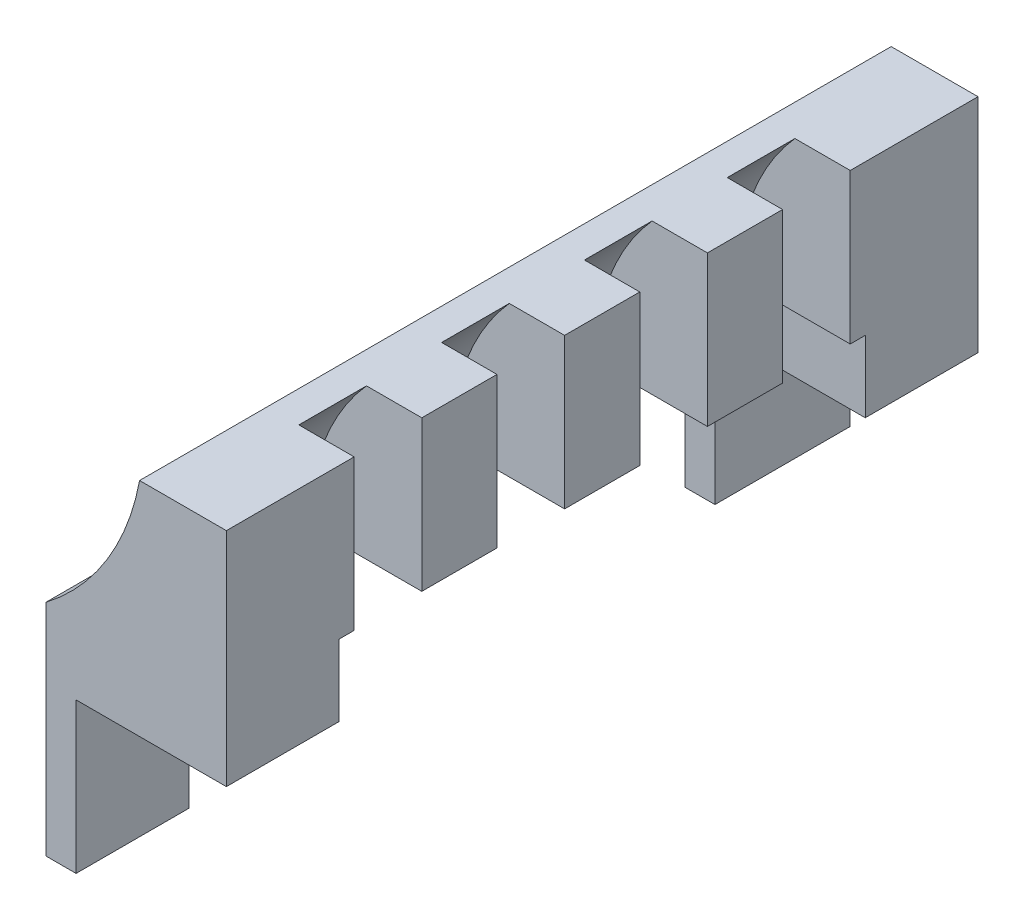
SolidWorks part; units mm, degrees
ref_plane "Front Plane" through (0, 0, 0) normal (0, 0, 1) x (1, 0, 0)
ref_plane "Top Plane" through (0, 0, 0) normal (0, 1, 0) x (1, 0, 0)
ref_plane "Right Plane" through (0, 0, 0) normal (1, 0, 0) x (0, 0, -1)
other "Configuration Table"
sketch "Sketch1" plane through (0, 0, 0) normal (0, 0, 1) x (1, 0, 0)
  line L0 (2, 14.75) -> (22, 14.75) construction
  line L1 (-2, -14.75) -> (2, -14.75)
  line L2 (-2, -14.75) -> (-2, 14.5012)
  line L3 (-1.6776, 14.75) -> (2, 14.75) construction
  line L4 (2, -14.75) -> (2, 5.25)
  line L5 (-2, -14.75) -> (2, 14.75) construction
  line L6 (-1.9694, 14.5245) -> (2, -14.75) construction
  line L7 (22, 14.75) -> (22, 5.25)
  line L8 (22, 5.25) -> (2, 5.25)
  line L9 (-2, 14.75) -> (-2, 15.75) construction
  line L10 (10.45, 34.75) -> (22, 34.75)
  line L11 (22, 34.75) -> (22, 14.75)
  line L12 (2, 5.25) -> (2, 14.75) construction
  line L13 (22, 5.25) -> (37, 5.25) construction
  line L14 (37, 5.25) -> (37, 14.75) construction
  line L15 (-2, 15.75) -> (3, 15.75) construction
  line L16 (3, 19.2093) -> (3, 34.75) construction
  line L17 (-2, 15.75) -> (-2, 34.75) construction
  line L18 (-2, 34.75) -> (3, 34.75) construction
  line L19 (-2, 15.75) -> (-2, 14.75) construction
  line L20 (3, 15.75) -> (3, 19.2093) construction
  line L21 (3, 34.75) -> (10.45, 34.75) construction
  line L22 (-2, 14.5012) -> (-2, 14.75) construction
  line L23 (-2, 14.5012) -> (-2, 14.75) construction
  line L24 (-2, 14.75) -> (-2, 14.5012) construction
  line L25 (-2, 14.75) -> (-1.9694, 14.5245) construction
  line L26 (-2, 14.75) -> (-1.6776, 14.75) construction
  line L27 (-2, 14.75) -> (-2, 15.75) construction
  circle A0 centre (37, 14.75) radius 30 construction
  arc A1 (-2, 14.5012) -> (10.45, 34.75) centre (-22, 40.75) ccw
  arc A2 (10.45, 34.75) -> (-2, 14.5012) centre (-22, 40.75) ccw construction
  point P0 (0, 0)
  dimension "D8" = 60
  dimension "D9" = 1
  dimension "D12" = 66
  dimension "D1" = 20
  dimension "D2" = 4
  dimension "D3" = 20
  dimension "D4" = 5
  dimension "D5" = 20
  dimension "D6" = 15
  dimension "D7" = 9.5
  dimension "D10" = 26
  dimension "D11" = 59
extrude "Boss-Extrude1" add sketch "Sketch1" along normal blind 50 and the other way blind 50
sketch "Sketch2" plane through (-2, 0, 0) normal (1, 0, 0) x (0, 0, -1)
  line L1 (-35, -14.75) -> (35, -14.75)
  line L2 (-35, -14.75) -> (-35, 14.75)
  line L3 (-35, 14.75) -> (35, 14.75)
  line L4 (35, -14.75) -> (35, 14.75)
  line L10 (50, 34.75) -> (-50, 34.75) construction
  line L11 (50, -14.75) -> (-50, -14.75) construction
  line L12 (-50, -14.75) -> (-50, 5.25) construction
  line L13 (50, -14.75) -> (50, 5.25) construction
  dimension "D1" = 15
  dimension "D2" = 15
  dimension "D3" = 20
extrude "Cut-Extrude1" cut sketch "Sketch2" against normal through all both and the other way through all
sketch "Sketch5" plane through (0, 34.75, 0) normal (0, 1, 0) x (1, 0, 0)
  line L0 (7, 0) -> (67, 0) construction
  line L1 (7, 0) -> (67, 0) construction
  line L2 (22, 50) -> (10.45, 50) construction
  line L3 (7, 50) -> (22, 50) construction
  line L4 (7, 50) -> (7, 33) construction
  line L5 (7, -50) -> (22, -50) construction
  line L6 (22, 50) -> (22, 33) construction
  line L7 (7, -33) -> (22, -33)
  line L8 (7, -24) -> (22, -24)
  line L9 (7, -14) -> (22, -14)
  line L10 (7, -5) -> (22, -5)
  line L11 (7, 5) -> (22, 5)
  line L12 (7, 14) -> (22, 14)
  line L13 (7, 24) -> (22, 24)
  line L14 (7, 33) -> (22, 33)
  line L15 (7, -24) -> (7, -33)
  line L16 (7, -33) -> (7, -50) construction
  line L17 (7, -5) -> (7, -14)
  line L18 (7, -14) -> (7, -24) construction
  line L19 (7, 14) -> (7, 5)
  line L20 (7, 5) -> (7, -5) construction
  line L21 (7, 33) -> (7, 24)
  line L22 (7, 24) -> (7, 14) construction
  line L23 (22, -24) -> (22, -33)
  line L24 (22, -33) -> (22, -50) construction
  line L25 (22, -5) -> (22, -14)
  line L26 (22, -14) -> (22, -24) construction
  line L27 (22, 14) -> (22, 5)
  line L28 (22, 5) -> (22, -5) construction
  line L29 (22, 33) -> (22, 24)
  line L30 (22, 24) -> (22, 14) construction
  line L31 (-1.6776, 35) -> (22, 35) construction
  line L32 (-1.6776, -35) -> (22, -35) construction
  line L33 (-1.6776, 35) -> (22, 35) construction
  line L34 (-1.6776, -35) -> (22, -35) construction
  dimension "D1" = 9
  dimension "D2" = 180
  dimension "D3" = 10
extrude "Cut-Extrude2" cut sketch "Sketch5" against normal up to surface (20 mm away) up to face at (10.1612, 14.75, 0)
sketch "Sketch6" plane through (0, 0, 50) normal (0, 0, 1) x (1, 0, 0)
  line L0 (7, 14.75) -> (22, 14.75) construction
  line L1 (22, 34.75) -> (14.6393, 34.75) construction
  line L4 (7, 14.75) -> (22, 14.75)
  line L5 (22, 14.75) -> (22, 34.75)
  line L6 (22, 34.75) -> (10.45, 34.75)
  line L7 (7, 25.002) -> (7, 14.75)
  line L9 (22, 14.75) -> (22, 34.75) construction
  line L10 (14.6393, 34.75) -> (10.45, 34.75)
  line L11 (7, 25.002) -> (7, 14.75)
  circle A0 centre (37, 14.75) radius 30 construction
  arc A1 (14.6393, 34.75) -> (7, 14.75) centre (37, 14.75) ccw
  arc A2 (7, 14.75) -> (14.6393, 34.75) centre (37, 14.75) ccw construction
  arc A4 (7, 25.002) -> (10.45, 34.75) centre (-22, 40.75) ccw
  arc A5 (7, 25.002) -> (10.45, 34.75) centre (-22, 40.75) ccw
  point P2 (7.0012, 15.016)
  dimension "D1" = 0
extrude "Boss-Extrude3" add sketch "Sketch6" against normal up to surface (100 mm away) up to face at (8.0481, 9.1202, -50)
sketch "Sketch8" plane through (0, 0, -50) normal (0, 0, -1) x (-1, 0, 0)
  line L0 (-22, 5.25) -> (-22, 0.25) construction
  line L5 (-12, 0.25) -> (-2, 0.25)
  line L6 (-2, 5.25) -> (-2, 0.25) construction
  line L8 (-22, 0.25) -> (-12, 0.25) construction
  line L10 (-10.45, 34.75) -> (-22, 34.75)
  line L11 (-22, 34.75) -> (-22, 5.25)
  line L12 (-22, 5.25) -> (-2, 5.25)
  line L13 (-2, 5.25) -> (-2, -14.75)
  line L14 (-2, -14.75) -> (2, -14.75)
  line L15 (2, -14.75) -> (2, 14.5012)
  line L18 (-22, 5.25) -> (-2, 5.25) construction
  line L19 (-2, 0.25) -> (-2, -14.75)
  line L20 (-2, -14.75) -> (2, -14.75)
  line L21 (2, -14.75) -> (2, 14.5012)
  line L22 (-22, 34.75) -> (-22, 5.25) construction
  line L24 (-12, 0.25) -> (-12, 14.5012)
  line L25 (-12, 14.5012) -> (2, 14.5012)
  arc A1 (-10.45, 34.75) -> (2, 14.5012) centre (22, 40.75) ccw
  point P4 (0, 0)
  point P11 (0, 0)
  point P12 (0, 0)
  dimension "D2" = 5
  dimension "D3" = 0
  dimension "D1" = 0
extrude "Boss-Extrude4" add sketch "Sketch8" along normal blind 3
